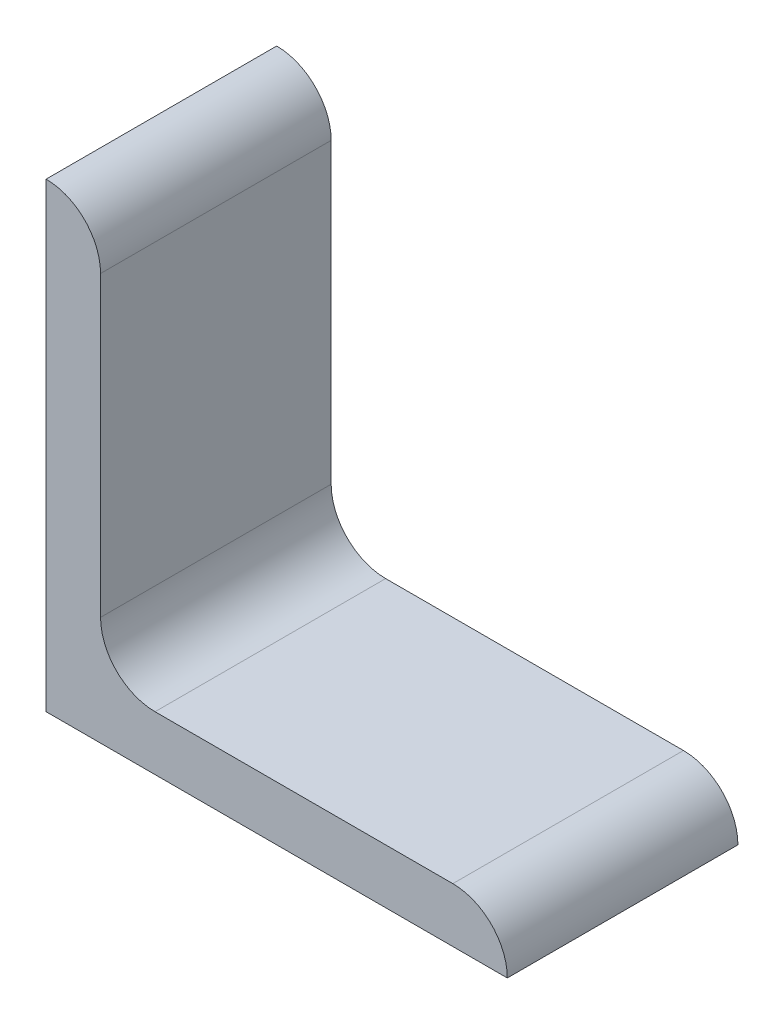
SolidWorks part; units mm, degrees
ref_plane "Plane1" through (0, 0, 0) normal (0, 0, 1) x (1, 0, 0)
ref_plane "Plane2" through (0, 0, 0) normal (0, 1, 0) x (1, 0, 0)
ref_plane "Plane3" through (0, 0, 0) normal (1, 0, 0) x (0, 0, -1)
sketch "Sketch1" plane through (0, 0, 0) normal (0, 0, 1) x (1, 0, 0)
  line L0 (0, 50.8) -> (0, 0)
  line L1 (0, 50.8) -> (9.525, 50.8) construction
  line L2 (6, 50.8) -> (6, 12)
  line L3 (12, 6) -> (50.8, 6)
  line L4 (50.8, 9.525) -> (50.8, 0) construction
  line L5 (50.8, 0) -> (0, 0)
  line L6 (50.8, 6) -> (50.8, 0)
  line L7 (0, 50.8) -> (6, 50.8)
  arc A2 (12, 6) -> (6, 12) centre (12, 12) cw
  dimension "Radius_1" = 6
  dimension "V_leg" = 50.8
  dimension "H_leg" = 50.8
extrude "BaseSteelAngle" add sketch "Sketch1" along normal mid plane 25.4
fillet "ToeFillet" radius 6 2 edges at (50.8, 6, 0) (6, 50.8, 0)
